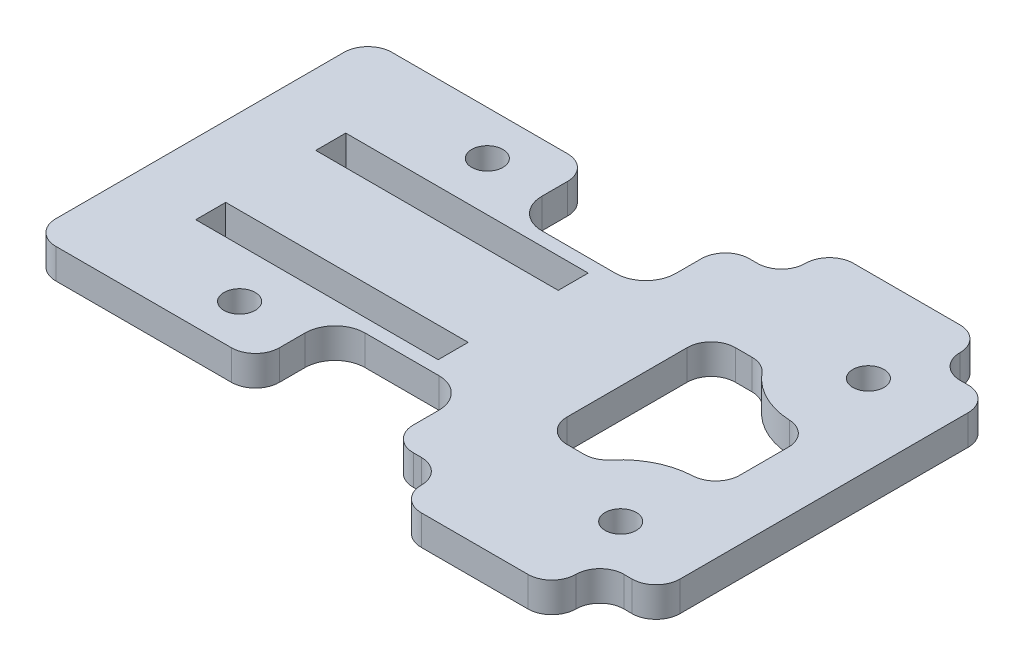
SolidWorks part; units mm, degrees
other "下垫片"
ref_plane "前视基准面" through (0, 0, 0) normal (0, 0, 1) x (1, 0, 0)
ref_plane "上视基准面" through (0, 0, 0) normal (0, 1, 0) x (1, 0, 0)
ref_plane "右视基准面" through (0, 0, 0) normal (1, 0, 0) x (0, 0, -1)
other "Configuration Table"
sketch "草图1" plane through (0, 0, 0) normal (0, 1, 0) x (1, 0, 0)
  line L0 (-89.3251, 0) -> (102.0425, 0) construction
  line L1 (0, 56.7239) -> (0, -62.578) construction
  line L2 (-47.2, -7.5) -> (-6.8, -7.5)
  line L3 (-47.2, 12.5) -> (-6.8, 12.5)
  line L4 (-47.2, 12.5) -> (-47.2, 7.5)
  line L5 (-47.2, 7.5) -> (-6.8, 7.5)
  line L6 (-6.8, 12.5) -> (-6.8, 7.5)
  line L7 (-47.2, 12.5) -> (-6.8, 7.5) construction
  line L8 (-47.2, 7.5) -> (-6.8, 12.5) construction
  line L9 (-6.8, -12.5) -> (-6.8, -7.5)
  line L10 (-47.2, -12.5) -> (-6.8, -12.5)
  line L11 (-47.2, -12.5) -> (-47.2, -7.5)
  line L14 (-21.75, -26.5375) -> (-21.75, -14.7375)
  line L15 (-21.75, -14.7375) -> (0.55, -14.7375)
  line L16 (0.55, -26.5375) -> (0.55, -14.7375)
  line L17 (-21.75, -26.5375) -> (0.55, -14.7375) construction
  line L18 (-21.75, -14.7375) -> (0.55, -26.5375) construction
  line L19 (-21.75, 14.7375) -> (0.55, 14.7375)
  line L20 (0.55, 26.5375) -> (0.55, 14.7375)
  line L22 (-21.75, 26.5375) -> (-21.75, 14.7375)
  line L23 (-21.75, 30.0095) -> (0.55, 30.0095)
  line L25 (-21.75, -26.5375) -> (-21.75, -30.0095)
  line L26 (-21.75, -30.0095) -> (0.55, -30.0095)
  line L27 (0.55, -26.5375) -> (0.55, -30.0095)
  line L28 (0.55, 26.5375) -> (0.55, 30.0095)
  line L30 (-21.75, 26.5375) -> (-21.75, 30.0095)
  circle A0 centre (-31.75, 20.6375) radius 2.6
  circle A4 centre (31.75, 20.6375) radius 2.6
  circle A5 centre (31.75, -20.6375) radius 2.6
  circle A6 centre (-31.75, -20.6375) radius 2.6
  point P13 (-27, 10)
  point P22 (-10.6, -20.6375)
  point P35 (-27, 10)
  dimension "D5" = 5.2
  dimension "D11" = 5.2
  dimension "D1" = 40.4
  dimension "D2" = 31.75
  dimension "D3" = 5
  dimension "D4" = 20.6375
  dimension "D6" = 10
  dimension "D7" = 22.3
  dimension "D8" = 11.8
  dimension "D9" = 0
  dimension "D10" = 31.2
  dimension "D12" = 5
  dimension "D13" = 40.4
  dimension "D14" = 27
  dimension "D15" = 10
  dimension "D16" = 2.2375
sketch "草图3" plane through (0, 0, 0) normal (0, 1, 0) x (1, 0, 0)
  line L0 (-40, 28) -> (-59, 28)
  line L1 (-40, -28) -> (9.9, -28)
  line L3 (-40, 28) -> (9.9, 28)
  line L5 (-40, -28) -> (40, 28) construction
  line L6 (-40, 28) -> (40, -28) construction
  line L7 (-59, 28) -> (-59, -28)
  line L8 (-59, -28) -> (-40, -28)
  line L10 (45, 28) -> (45, -28)
  line L15 (-45.7746, 0) -> (58.2399, 0) construction
  line L19 (9.9, 28) -> (9.9, 36)
  line L20 (9.9, 36) -> (35.65, 36)
  line L21 (35.65, 36) -> (35.65, 28)
  line L22 (35.65, 28) -> (45, 28)
  line L23 (35.65, -28) -> (45, -28)
  line L24 (35.65, -36) -> (35.65, -28)
  line L25 (9.9, -36) -> (35.65, -36)
  line L26 (9.9, -28) -> (9.9, -36)
  point P0 (0, 0)
  dimension "D1" = 56
  dimension "D2" = 80
  dimension "D3" = 19
  dimension "D4" = 5
  dimension "D5" = 9.35
  dimension "D6" = 8
  dimension "D7" = 25.75
extrude "凸台-拉伸1" add sketch "草图3" along normal blind 5
extrude "切除-拉伸1" cut sketch "草图1" along normal up to surface (5 mm away) up to face at (12.85, 5, 0)
fillet "圆角1" radius 5 4 edges at (0.55, 2.5, 14.7375) (-21.75, 2.5, 14.7375) (0.55, 2.5, -14.7375) (-21.75, 2.5, -14.7375)
fillet "圆角2" radius 4 16 edges at (0.55, 2.5, 28) (-21.75, 2.5, 28) (0.55, 2.5, -28) (-21.75, 2.5, -28) (-59, 2.5, 28) (-59, 2.5, -28) (9.9, 2.5, 28) (9.9, 2.5, 36) (35.65, 2.5, 36) (35.65, 2.5, 28) (45, 2.5, 28) (45, 2.5, -28) (35.65, 2.5, -28) (35.65, 2.5, -36) (9.9, 2.5, -36) (9.9, 2.5, -28)
sketch "草图14" plane through (0, 5, 0) normal (0, 1, 0) x (1, 0, 0)
  line L0 (-11.6114, 0) -> (10.899, 0) construction
  line L1 (21.04, 14) -> (12.2, 14)
  line L2 (12.2, 14) -> (12.2, -14)
  line L3 (45, -24) -> (45, 24) construction
  line L4 (35, 8.4639) -> (35, -8.4639)
  line L5 (21.04, -14) -> (12.2, -14)
  arc A0 (35, 8.4639) -> (21.04, 14) centre (31.75, 20.6375) cw
  arc A1 (35, -8.4639) -> (21.04, -14) centre (31.75, -20.6375) ccw
  point P5 (35, 0)
  point P7 (21.04, 14)
  point P8 (35, 8.4639)
  point P18 (12.2, 0)
  dimension "D1" = 12.6
  dimension "D2" = 14
  dimension "D3" = 12.2
  dimension "D4" = 10
extrude "切除-拉伸6" cut sketch "草图14" against normal through all
fillet "圆角5" radius 4 6 edges at (35, 2.5, 8.4639) (21.04, 2.5, 14) (12.2, 2.5, 14) (21.04, 2.5, -14) (35, 2.5, -8.4639) (12.2, 2.5, -14)
